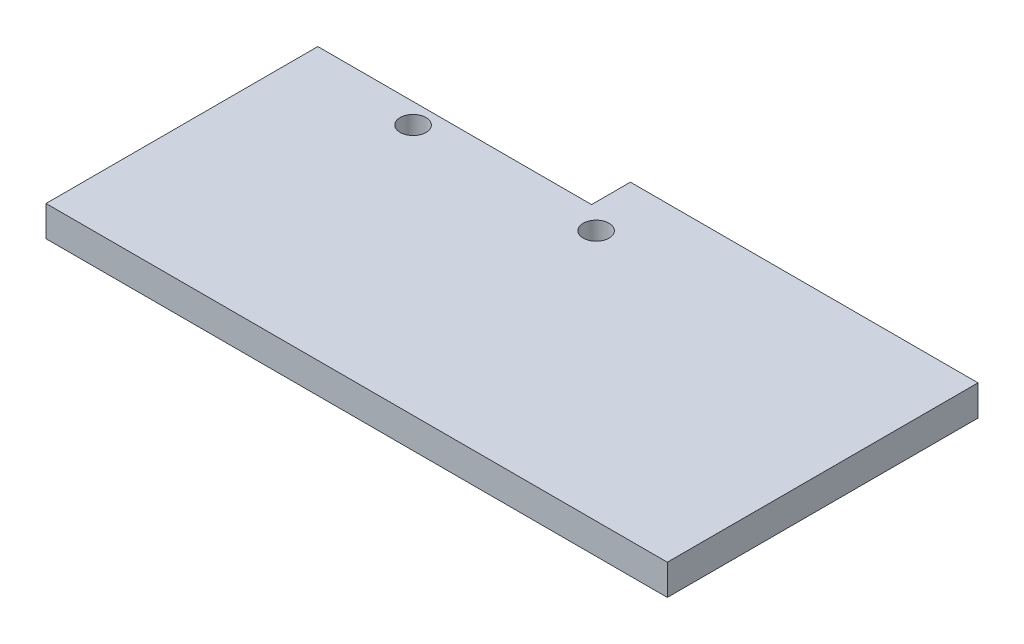
SolidWorks part; units mm, degrees
material "Wrought Stainless Steel"
ref_plane "Front Plane" through (0, 0, 0) normal (0, 0, 1) x (1, 0, 0)
ref_plane "Top Plane" through (0, 0, 0) normal (0, 1, 0) x (1, 0, 0)
ref_plane "Right Plane" through (0, 0, 0) normal (1, 0, 0) x (0, 0, -1)
sketch "Sketch1" plane through (0, 0, 0) normal (0, 1, 0) x (1, 0, 0)
  line L1 (-50.9391, 35.3639) -> (1168.2609, 35.3639)
  line L2 (-50.9391, 35.3639) -> (-50.9391, -574.2361)
  line L3 (-50.9391, -574.2361) -> (1168.2609, -574.2361)
  line L4 (1168.2609, 35.3639) -> (1168.2609, -574.2361)
  dimension "D1" = 1219.2
  dimension "D2" = 609.6
extrude "Extrude1" add sketch "Sketch1" along normal blind 59.944
sketch "Sketch8" plane through (0, 59.944, 0) normal (0, 1, 0) x (-1, 0, 0)
  line L0 (-1168.2609, -35.3639) -> (50.9391, -35.3639) construction
  line L1 (50.9391, -35.3639) -> (50.9391, 574.2361) construction
  point P0 (-355.4609, -98.8639)
  dimension "D1" = 63.5
  dimension "D2" = 406.4
ref_axis "Trap Axis" through (355.4609, 59.944, -98.8639) along (0, 1, 0)
sketch "Sketch9" plane through (0, 59.944, 0) normal (0, 1, 0) x (1, 0, 0)
  line L0 (355.4609, 98.8639) -> (355.4609, -259.5369) construction
  line L1 (372.9778, 55.4152) -> (133.7933, 55.4152) construction
  line L2 (486.1754, 55.4152) -> (486.1754, -40.8361)
  line L3 (486.1754, -40.8361) -> (-155.1152, -40.8361)
  line L4 (-155.1152, -40.8361) -> (-155.1152, 55.4152)
  line L5 (-155.1152, 55.4152) -> (486.1754, 55.4152)
  dimension "D1" = 96.2513
  dimension "D2" = 139.7
extrude "Extrude2" cut sketch "Sketch9" against normal through all
sketch "Sketch10" plane through (0, 59.944, 0) normal (0, 1, 0) x (1, 0, 0)
  line L0 (355.4609, 98.8639) -> (355.4609, -210.3635) construction
  line L1 (428.8705, 172.2735) -> (147.2025, -109.3944) construction
  circle A0 centre (175.8557, -80.7412) radius 25.4
  circle A1 centre (535.066, -80.7412) radius 25.4
  dimension "D2" = 50.8
  dimension "D1" = 45
  dimension "D3" = 254
extrude "Extrude3" cut sketch "Sketch10" against normal through all
